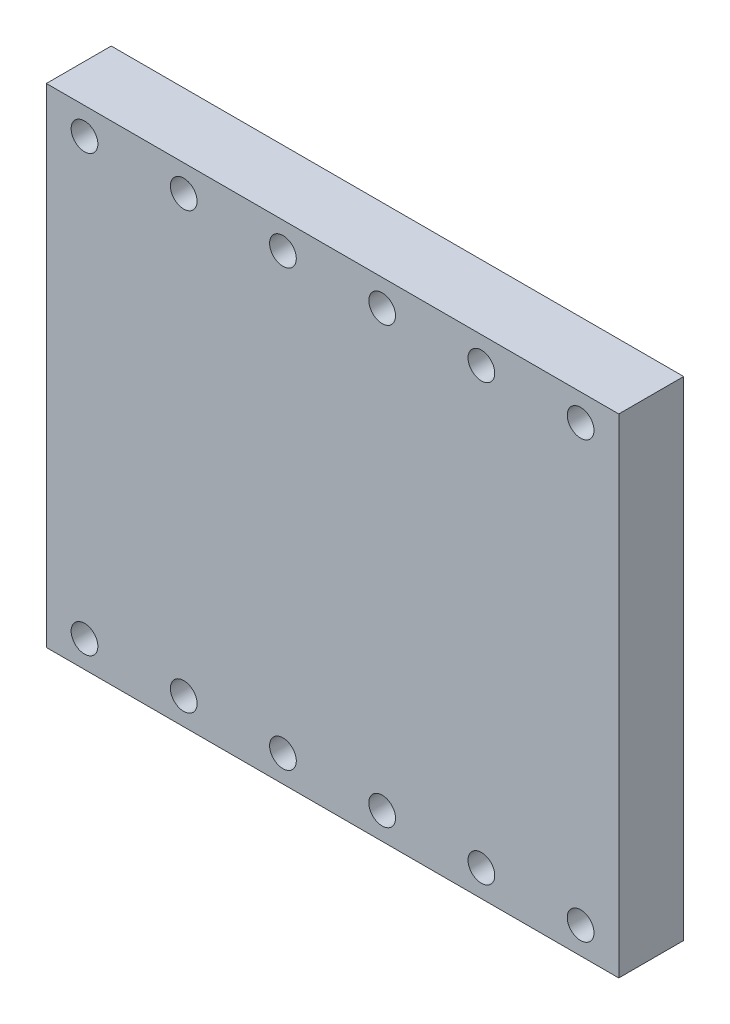
SolidWorks part; units mm, degrees
ref_plane "Front Plane" through (0, 0, 0) normal (0, 0, 1) x (1, 0, 0)
ref_plane "Top Plane" through (0, 0, 0) normal (0, 1, 0) x (1, 0, 0)
ref_plane "Right Plane" through (0, 0, 0) normal (1, 0, 0) x (0, 0, -1)
sketch "Sketch1" plane through (0, 0, 0) normal (0, 0, 1) x (1, 0, 0)
  line L0 (0, 8.9048) -> (0, -10.0107) construction
  line L1 (-7.5, 6.4) -> (7.5, 6.4)
  line L2 (-7.5, 6.4) -> (-7.5, -6.4)
  line L3 (-7.5, -6.4) -> (7.5, -6.4)
  line L4 (7.5, 6.4) -> (7.5, -6.4)
  line L5 (-10.6092, 0) -> (11.6306, 0) construction
  line L6 (-3, 0.6) -> (-1, 0.6)
  line L7 (-7, 0.6) -> (-5, 0.6)
  line L8 (-7, 0.6) -> (-7, -0.6)
  line L9 (-7, -0.6) -> (-5, -0.6)
  line L10 (-5, 0.6) -> (-5, -0.6)
  line L11 (-1, 0.6) -> (-1, -0.6)
  line L12 (-3, -0.6) -> (-1, -0.6)
  line L13 (-3, 0.6) -> (-3, -0.6)
  line L14 (1, 0.6) -> (3, 0.6)
  line L15 (3, 0.6) -> (3, -0.6)
  line L16 (1, -0.6) -> (3, -0.6)
  line L17 (1, 0.6) -> (1, -0.6)
  line L18 (5, 0.6) -> (7, 0.6)
  line L19 (7, 0.6) -> (7, -0.6)
  line L20 (5, -0.6) -> (7, -0.6)
  line L21 (5, 0.6) -> (5, -0.6)
  circle A0 centre (-6.5, 5.7) radius 0.35
  circle A1 centre (-3.9, 5.7) radius 0.35
  circle A2 centre (-1.3, 5.7) radius 0.35
  circle A3 centre (1.3, 5.7) radius 0.35
  circle A4 centre (3.9, 5.7) radius 0.35
  circle A5 centre (6.5, 5.7) radius 0.35
  circle A6 centre (-1.3, -5.7) radius 0.35
  circle A7 centre (6.5, -5.7) radius 0.35
  circle A8 centre (3.9, -5.7) radius 0.35
  circle A9 centre (1.3, -5.7) radius 0.35
  circle A10 centre (-3.9, -5.7) radius 0.35
  circle A11 centre (-6.5, -5.7) radius 0.35
  point P29 (0, 0)
  point P38 (-6.173, 5.7)
  dimension "D7" = 0.7
  dimension "D1" = 15
  dimension "D2" = 12.8
  dimension "D3" = 1.2
  dimension "D4" = 2
  dimension "D5" = 4
  dimension "D6" = 14
  dimension "D8" = 0.7
  dimension "D10" = 13
  dimension "D9" = 6
extrude "Boss-Extrude1" add sketch "Sketch1" along normal blind 1.7 contours L2 L3 L4 L1
extrude "Boss-Extrude2" add sketch "Sketch1<3>" against normal blind 0.5 contours L10 L9 L8 L7 | L11 L12 L13 L6 | L14 L15 L16 L17 | L18 L19 L20 L21
sketch "Sketch1<3>" plane through (0, 0, 0) normal (0, 0, 1) x (1, 0, 0) same geometry as "Sketch1"
extrude "Cut-Extrude1" cut sketch "Sketch1<4>" along normal through all contours A2 | A1 | A0 | A5 | A4 | A3 | A6 | A9 | A8 | A7 | A11 | A10
sketch "Sketch1<4>" plane through (0, 0, 0) normal (0, 0, 1) x (1, 0, 0) same geometry as "Sketch1"
